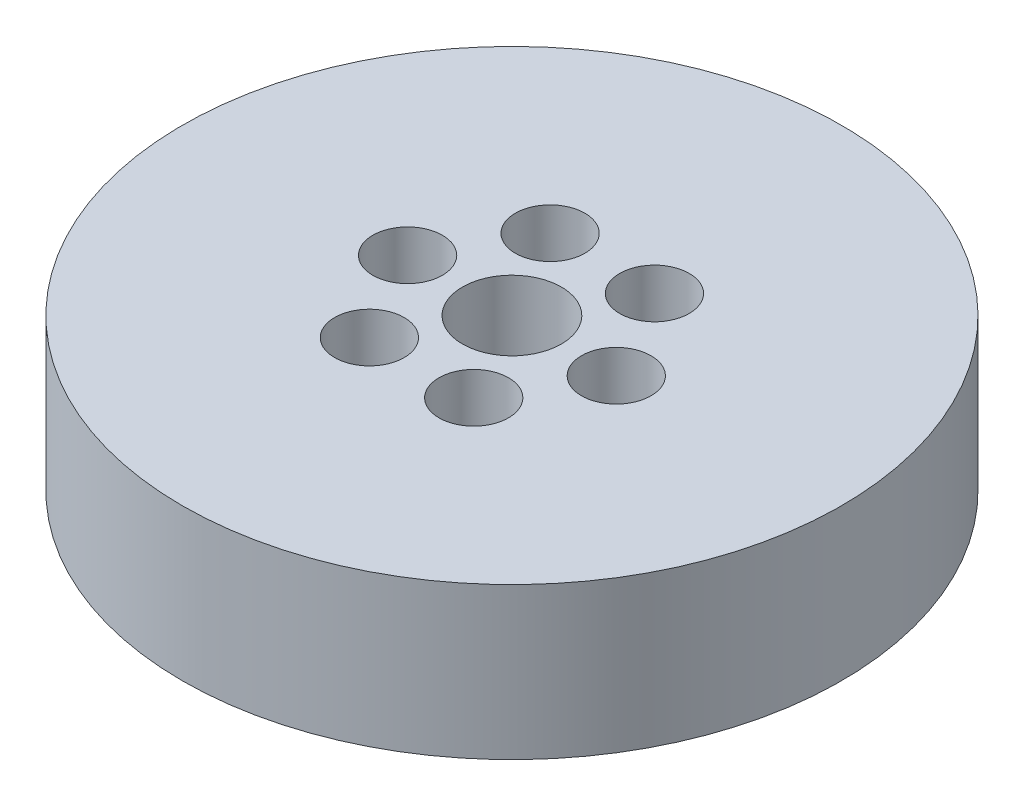
SolidWorks part; units mm, degrees
ref_plane "Front Plane" through (0, 0, 0) normal (0, 0, 1) x (1, 0, 0)
ref_plane "Top Plane" through (0, 0, 0) normal (0, 1, 0) x (1, 0, 0)
ref_plane "Right Plane" through (0, 0, 0) normal (1, 0, 0) x (0, 0, -1)
sketch "Sketch1" plane through (0, 0, 0) normal (0, 1, 0) x (1, 0, 0)
  circle A0 centre (0, 0) radius 50
  dimension "FLANGE_OD" = 100
extrude "Boss-Extrude1" add sketch "Sketch1" along normal blind 23
sketch "Sketch2" plane through (0, 0, 0) normal (0, 1, 0) x (1, 0, 0)
  circle A0 centre (0, 0) radius 7.5
  dimension "BORE_D" = 15
extrude "Cut-Extrude1" cut sketch "Sketch2" along normal through all
sketch "Sketch3" plane through (0, 23, 0) normal (0, 1, 0) x (1, 0, 0)
  circle A0 centre (0, 0) radius 15.8285 construction
  circle A1 centre (-15.8285, 0) radius 5.2737
  dimension "BOLT_D" = 10.5474
  dimension "BOLT_PCD" = 31.657
extrude "Cut-Extrude2" cut sketch "Sketch3" against normal blind 22.2061
pattern_circular "CirPattern1" count 6 over 360 about axis through (0, 0, 0) along (0, 1, 0) of "Cut-Extrude2"
